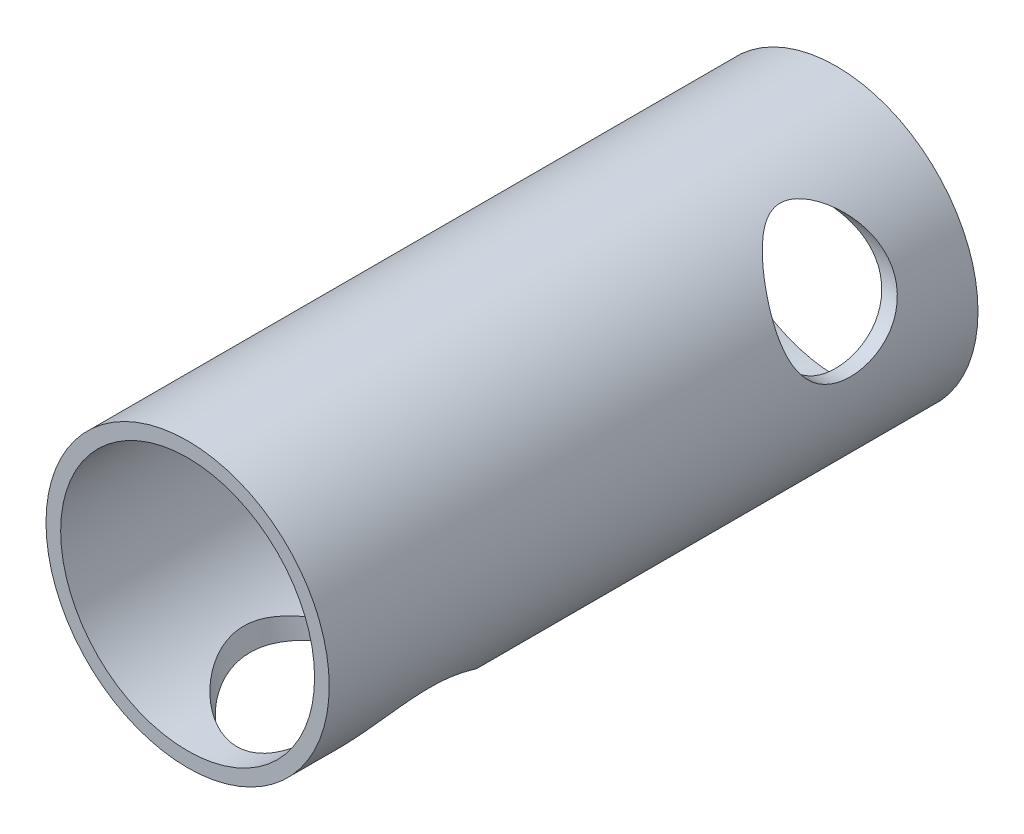
SolidWorks part; units mm, degrees
ref_plane "Front Plane" through (0, 0, 0) normal (0, 0, 1) x (1, 0, 0)
ref_plane "Top Plane" through (0, 0, 0) normal (0, 1, 0) x (1, 0, 0)
ref_plane "Right Plane" through (0, 0, 0) normal (1, 0, 0) x (0, 0, -1)
sketch "Sketch1" plane through (0, 0, 0) normal (0, 0, 1) x (1, 0, 0)
  line L0 (-0.0494, 0) -> (-22.2407, -0.9122)
  circle A0 centre (-0.0494, 0) radius 22.21
  circle A1 centre (-0.0494, 0) radius 19.91
  point P4 (-13.1198, -17.9569)
  dimension "D1" = 44.42
  dimension "D2" = 39.82
extrude "Boss-Extrude1" add sketch "Sketch1" along normal blind 101.75 contours A1 A0 | A0 | A1 region at (-0.4927, 21.5773, 0)
sketch "Sketch2" plane through (0, 0, 101.75) normal (0, 0, 1) x (1, 0, 0)
  line L0 (0, 0) -> (6.8585, -21.1084)
  line L1 (0, 0) -> (22.1606, 0)
  circle A1 centre (-0.0494, 0) radius 22.21 construction
  dimension "D1" = 72
ref_plane "Plane1" through (6.8585, -21.1084, 101.75) normal (0.311, -0.9504, 0) x (-0.9504, -0.311, 0)
ref_plane "Plane2" through (22.1606, 0, 101.75) normal (1, 0, 0) x (0, 0, -1)
sketch "Sketch4" plane through (22.1606, 0, 101.75) normal (1, 0, 0) x (0, 0, -1)
  line L0 (101.75, -22.21) -> (101.75, 22.21) construction
  line L1 (101.75, 22.21) -> (0, 22.21) construction
  circle A0 centre (81.75, 10.1535) radius 9.0424
  dimension "D1" = 18.0848
  dimension "D2" = 20
  dimension "D3" = 12.0565
sketch "Sketch5" plane through (6.8585, -21.1084, 101.75) normal (0.311, -0.9504, 0) x (-0.9504, -0.311, 0)
  line L0 (-0.047, 0) -> (-21.1084, 0) construction
  circle A0 centre (-0.0494, 18.7) radius 14.8463
  dimension "D1" = 29.6926
  dimension "D2" = 18.7
extrude "Cut-Extrude2" cut sketch "Sketch5" against normal up to next contours A0
extrude "Cut-Extrude3" cut sketch "Sketch4" against normal up to next contours A0
equation "\"can_outer_diameter\"= 44.42mm"
equation "\"D1@Sketch1\"=\"can_outer_diameter\""
equation "\"can_thickness\"= 2.3"
equation "\"D2@Sketch1\"=\"can_outer_diameter\"-2*\"can_thickness\""
equation "\"can_height\"= 5.75in - 44.3mm"
equation "\"D1@Boss-Extrude1\"=\"can_height\""
equation "\"inlet_diameter\"= 0.712in"
equation "\"D1@Sketch4\"=\"inlet_diameter\""
equation "\"outlet_diameter\"= 1.169in"
equation "\"D1@Sketch5\"=\"outlet_diameter\""
equation "\"D2@Sketch5\"=6mm+12.7"
equation "\"D3@Sketch4\"=\"inlet_diameter\"/1.5"
